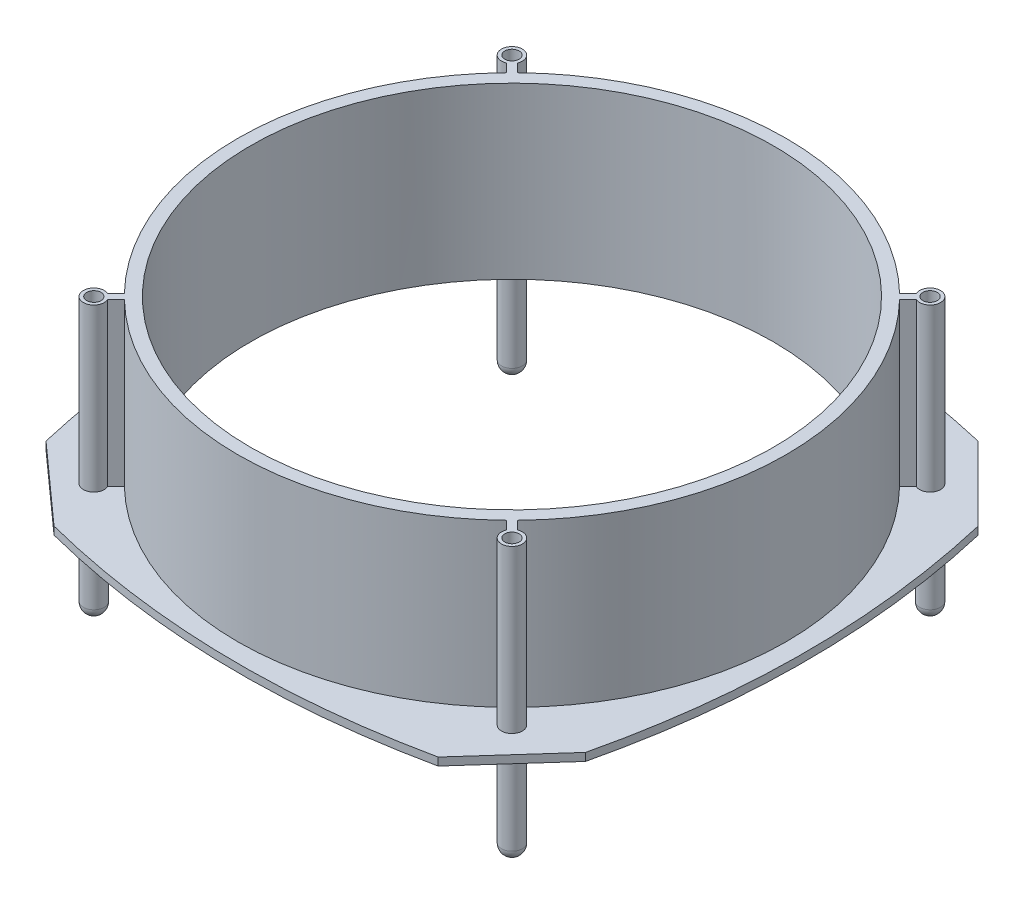
SolidWorks part; units mm, degrees
ref_plane "Front Plane" through (0, 0, 0) normal (0, 0, 1) x (1, 0, 0)
ref_plane "Top Plane" through (0, 0, 0) normal (0, 1, 0) x (1, 0, 0)
ref_plane "Right Plane" through (0, 0, 0) normal (1, 0, 0) x (0, 0, -1)
sketch "Sketch2" plane through (0, 0, 0) normal (0, 1, 0) x (1, 0, 0)
  line L0 (3824.4294, -5236.7276) -> (5157.6927, -3749.6242)
  line L2 (5163.9685, 3752.3444) -> (3751.2089, 5164.1439)
  line L4 (-3751.7702, 5163.5828) -> (-5163.7079, 3750.9614)
  line L6 (-5163.0762, -3751.9198) -> (-3675.9728, -5085.183)
  circle A0 centre (0, 0) radius 5000
  spline S0 degree 2 poles (-3751.7702, 5163.5828) (-0.3376, 6037.3855) (3751.2089, 5164.1439) knots 0 0 0 1 1 1
  spline S1 degree 2 poles (-5163.7079, 3750.9614) (-6037.5496, -0.539) (-5163.0762, -3751.9198) knots 0 0 0 1 1 1
  spline S2 degree 2 poles (-3675.9728, -5085.183) (54.6713, -6041.0227) (3824.4294, -5236.7276) knots 0 0 0 1 1 1
  spline S3 degree 2 poles (5163.9685, 3752.3444) (6040.8667, 0.5969) (5157.6927, -3749.6242) knots 0 0 0 1 1 1
extrude "Boss-Extrude2" add sketch "Sketch2" along normal blind 150
sketch "Sketch3" plane through (0, 0, 0) normal (0, 1, 0) x (1, 0, 0)
  circle A0 centre (0, 0) radius 5244.2465
extrude "Boss-Extrude3" add sketch "Sketch3" along normal blind 3250
sketch "Sketch5" plane through (0, 150, 0) normal (0, 1, 0) x (1, 0, 0)
  circle A0 centre (-4000, -4000) radius 250
  circle A1 centre (4000, -4000) radius 250
  circle A2 centre (4000, 4000) radius 250
sketch "Sketch7" plane through (0, 0, 0) normal (0, -1, 0) x (-1, 0, 0)
  circle A0 centre (4000, 4000) radius 200
sketch "Sketch8" plane through (0, 150, 0) normal (0, 1, 0) x (1, 0, 0)
  line L0 (3785.2923, -3871.9351) -> (3569.5398, -3651.2442)
  circle A0 centre (4000, -4000) radius 250 construction
  point P0 (3786.5537, -3873.2254)
  point P4 (3786.5537, -3873.2254)
  point P5 (3786.5537, -3873.2254)
  point P6 (3888.8138, -3773.2537)
  point P11 (3890.7516, -3775.1339)
extrude "Extrude-Thin9" [suppressed] add sketch "Sketch8" along normal blind 2400 thin thin type one direction wall 128
extrude "Boss-Extrude11" [suppressed] add sketch "Sketch5" along normal blind 2850 and the other way blind 1900 contours A1
sketch "Sketch9" plane through (0, 0, 0) normal (0, -1, 0) x (-1, 0, 0)
  circle A0 centre (4000, 4000) radius 200
extrude "Boss-Extrude12" add sketch "Sketch7" against normal blind 3250 contours A0
extrude "Boss-Extrude13" add sketch "Sketch9" along normal blind 2000 contours A0
fillet "Fillet1" radius 200 2 edges at (-4000, 0, -4200) (-4000, -2000, -4200)
sketch "Sketch10" plane through (0, 3250, 0) normal (0, 1, 0) x (1, 0, 0)
  circle A0 centre (-4000, 4000) radius 137.4456
extrude "Cut-Extrude2" cut sketch "Sketch10" against normal blind 500
sketch "Sketch13" plane through (0, 150, 0) normal (0, 1, 0) x (1, 0, 0)
  line L0 (-3817.1489, 3918.9723) -> (-3656.9811, 3758.8045)
  line L1 (-3758.8045, 3656.9811) -> (-3918.9723, 3817.1489)
  circle A0 centre (-4000, 4000) radius 200 construction
  circle A1 centre (0, 0) radius 5244.2465 construction
  dimension "D1" = 144
extrude "Extrude-Thin10" add sketch "Sketch13" along normal blind 3100 thin thin type one direction wall 72
ref_axis "Axis1" through (0, 3250, 0) along (0, -1, 0)
pattern_circular "CirPattern1" count 4 over 360 about axis through (0, 3250, 0) along (0, -1, 0) of "Boss-Extrude12", "Boss-Extrude13", "Fillet1", "Cut-Extrude2", "Extrude-Thin10"
scale "Scale2" scale about origin uniform scaling yes scale factor 0.01
sketch "Sketch14" plane through (0, 32.5, 0) normal (0, 1, 0) x (1, 0, 0)
  circle A0 centre (0, 0) radius 50
extrude "Cut-Extrude4" cut sketch "Sketch14" against normal through all
